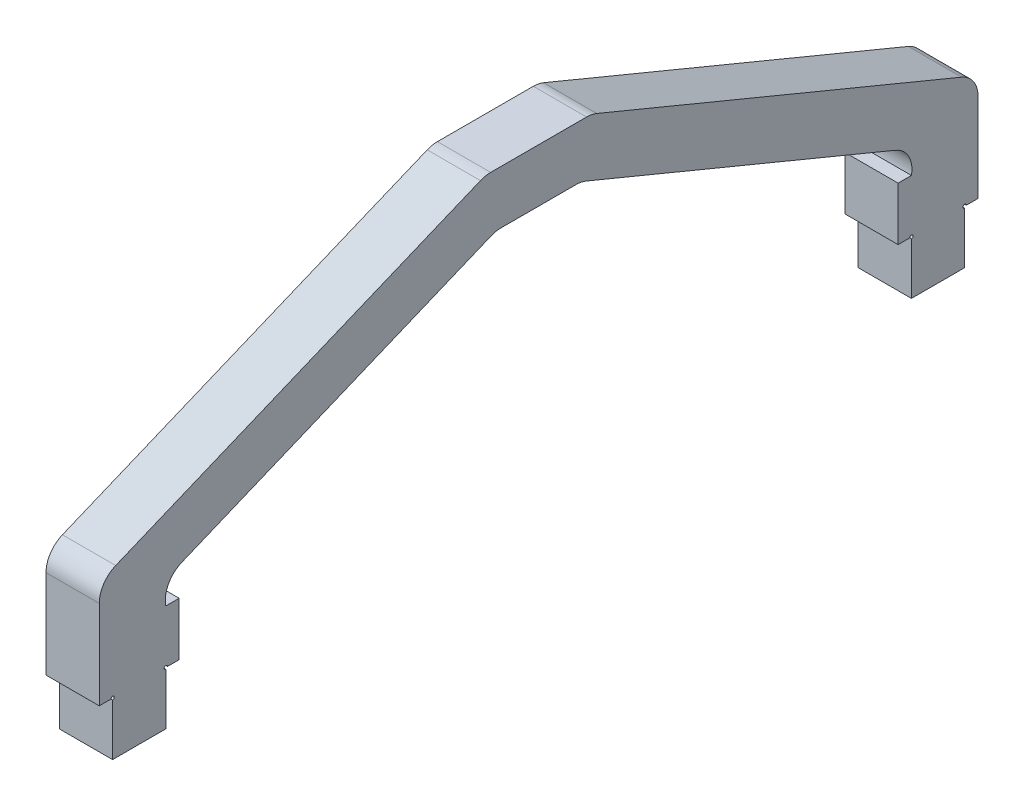
SolidWorks part; units mm, degrees
ref_plane "Front Plane" through (0, 0, 0) normal (0, 0, 1) x (1, 0, 0)
ref_plane "Top Plane" through (0, 0, 0) normal (0, 1, 0) x (1, 0, 0)
ref_plane "Right Plane" through (0, 0, 0) normal (1, 0, 0) x (0, 0, -1)
sketch "Sketch1" plane through (0, 0, 0) normal (1, 0, 0) x (0, 0, -1)
  line L0 (0, 0) -> (0, 25.4) construction
  line L1 (44.45, 0) -> (42.8625, 0) construction
  line L2 (50.8, 0) -> (52.3875, 0)
  line L3 (52.3875, 0) -> (52.3875, 12.7)
  line L4 (-50.8, 0) -> (-50.8, -6.35)
  line L5 (-50.8, -6.35) -> (-44.45, -6.35)
  line L6 (-44.45, 0) -> (-44.45, -6.35)
  line L7 (50.8, 0) -> (50.8, -6.35)
  line L8 (50.8, -6.35) -> (44.45, -6.35)
  line L9 (44.45, 0) -> (44.45, -6.35)
  line L10 (-44.45, 0) -> (-42.8625, 0)
  line L11 (5.0881, 25.4) -> (-6.35, 25.4)
  line L12 (6.35, 31.75) -> (-6.35, 31.75)
  line L13 (6.35, 31.75) -> (52.3875, 12.7)
  line L14 (-44.45, 6.35) -> (-42.8625, 6.35)
  line L15 (5.0881, 25.4) -> (46.0375, 8.4554)
  line L16 (44.45, 6.35) -> (46.0375, 8.4554)
  line L17 (3.9221, 25.8825) -> (46.0375, 8.4554) construction
  line L18 (6.35, 25.4) -> (-6.35, 25.4) construction
  line L19 (46.0375, 0) -> (46.0375, 8.4554) construction
  line L20 (-6.35, 31.75) -> (-52.3875, 12.7)
  line L21 (-52.3875, 0) -> (-52.3875, 12.7)
  line L22 (-44.45, 6.35) -> (-46.0375, 8.4554)
  line L23 (-5.0881, 25.4) -> (-46.0375, 8.4554)
  line L24 (-50.8, 0) -> (-52.3875, 0)
  line L25 (-42.8625, 0) -> (-42.8625, 6.35)
  line L26 (42.8625, 0) -> (42.8625, 6.35)
  line L27 (42.8625, 6.35) -> (44.45, 6.35)
  line L28 (42.8625, 0) -> (44.45, 0)
  line L29 (-44.45, 6.35) -> (44.45, 6.35) construction
  line L30 (0, 0) -> (-44.45, 0) construction
  line L31 (-44.45, 0) -> (44.45, 0) construction
  point P6 (0, 0)
  point P17 (0, 25.4)
  dimension "D1" = 25.4
  dimension "D2" = 101.6
  dimension "D3" = 6.35
  dimension "D4" = 6.35
  dimension "D5" = 1.5875
  dimension "D6" = 6.35
  dimension "D8" = 12.7
  dimension "D10" = 1.5875
  dimension "D7" = 6.35
  dimension "D9" = 6.35
extrude "Boss-Extrude1" add sketch "Sketch1" along normal blind 6.35 contours L24 L4 L5 L6 L10 L9 L8 L7 L2 L3 L13 L12 L20 L21 L23 L11 L15 L16 L14 L22 region at (0, -3.175, -49.6851)
sketch "Sketch2" plane through (6.35, 0, 0) normal (1, 0, 0) x (0, 0, -1)
  line L0 (0, 31.75) -> (0, 0) construction
  line L1 (6.35, 31.75) -> (-6.35, 31.75) construction
  circle A0 centre (-50.8, 0) radius 0.1984
  circle A1 centre (-44.45, 0) radius 0.1984
  circle A2 centre (44.45, 0) radius 0.1984
  circle A3 centre (50.8, 0) radius 0.1984
  dimension "D1" = 0.3969
  dimension "D2" = 0.3969
extrude "Cut-Extrude1" cut sketch "Sketch2" against normal through all
fillet "Fillet5" radius 3.175 8 edges at (3.175, 8.4554, 46.0375) (3.175, 8.4554, -46.0375) (3.175, 12.7, -52.3875) (3.175, 31.75, -6.35) (3.175, 25.4, -5.0881) (3.175, 25.4, 5.0881) (3.175, 31.75, 6.35) (3.175, 12.7, 52.3875)
